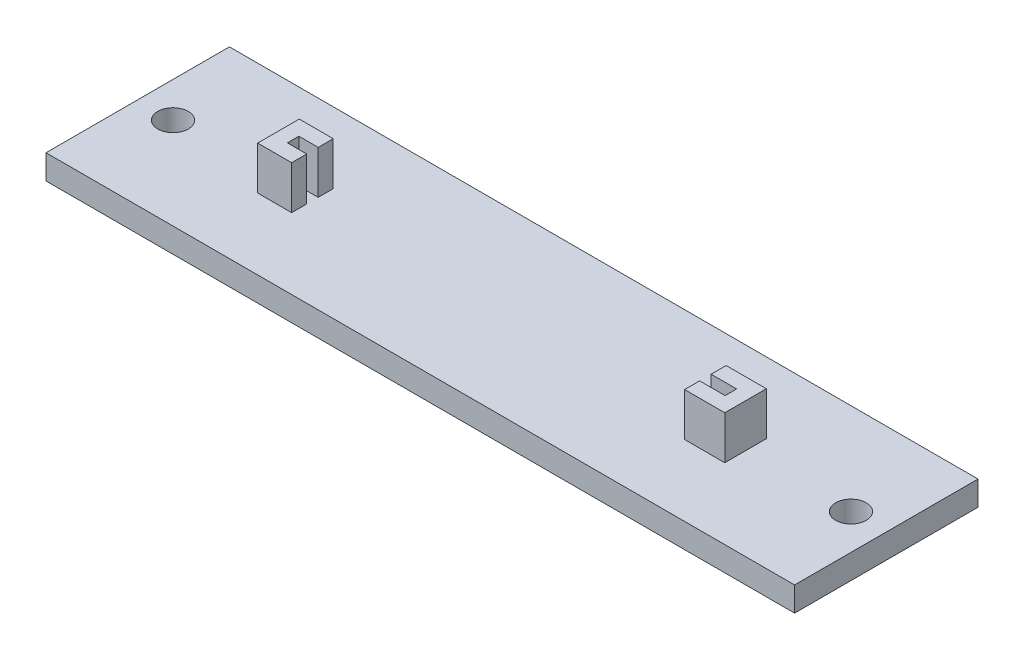
SolidWorks part; units mm, degrees
ref_plane "Front Plane" through (0, 0, 0) normal (0, 0, 1) x (1, 0, 0)
ref_plane "Top Plane" through (0, 0, 0) normal (0, 1, 0) x (1, 0, 0)
ref_plane "Right Plane" through (0, 0, 0) normal (1, 0, 0) x (0, 0, -1)
sketch "Sketch1" plane through (0, 0, 0) normal (0, 1, 0) x (1, 0, 0)
  line L1 (-38.875, 9.525) -> (38.875, 9.525)
  line L2 (-38.875, 9.525) -> (-38.875, -9.525)
  line L3 (-38.875, -9.525) -> (38.875, -9.525)
  line L4 (38.875, 9.525) -> (38.875, -9.525)
  line L5 (-38.875, 9.525) -> (38.875, -9.525) construction
  line L6 (-38.875, -9.525) -> (38.875, 9.525) construction
  point P0 (0, 0)
  dimension "D1" = 19.05
  dimension "D2" = 77.75
extrude "Boss-Extrude1" add sketch "Sketch1" along normal blind 2.54
sketch "Sketch2" plane through (0, 2.54, 0) normal (0, 1, 0) x (1, 0, 0)
  line L0 (38.875, 0) -> (36.7922, 0) construction
  line L1 (38.875, -9.525) -> (38.875, 9.525) construction
  line L2 (36.7922, 0) -> (35.2047, 0) construction
  line L3 (-38.875, 0) -> (-36.7922, 0) construction
  line L4 (-38.875, 9.525) -> (-38.875, -9.525) construction
  line L5 (-36.7922, 0) -> (-35.2047, 0) construction
  circle A0 centre (35.2047, 0) radius 1.5875
  circle A1 centre (-35.2047, 0) radius 1.5875
  dimension "D1" = 2.0828
  dimension "D2" = 1.5875
  dimension "D3" = 2.0828
  dimension "D4" = 1.5875
extrude "Cut-Extrude1" cut sketch "Sketch2" against normal through all
sketch "Sketch3" plane through (0, 2.54, 0) normal (0, 1, 0) x (1, 0, 0)
  line L1 (-24.257, 2.159) -> (24.257, 2.159)
  line L2 (-24.257, 2.159) -> (-24.257, -2.159)
  line L3 (-24.257, -2.159) -> (24.257, -2.159)
  line L4 (24.257, 2.159) -> (24.257, -2.159)
  line L5 (-24.257, 2.159) -> (24.257, -2.159) construction
  line L6 (-24.257, -2.159) -> (24.257, 2.159) construction
  point P0 (0, 0)
  dimension "D1" = 48.514
  dimension "D2" = 4.318
extrude "Boss-Extrude2" add sketch "Sketch3" along normal blind 4.4958
sketch "Sketch4" plane through (0, 7.0358, 0) normal (0, 1, 0) x (1, 0, 0)
  line L0 (-22.733, -2.159) -> (-20.7264, -2.159) construction
  line L1 (-22.733, 0.5969) -> (22.733, 0.5969)
  line L2 (-22.733, 0.5969) -> (-22.733, -0.5969)
  line L3 (-22.733, -0.5969) -> (22.733, -0.5969)
  line L4 (22.733, 0.5969) -> (22.733, -0.5969)
  line L5 (-22.733, 0.5969) -> (22.733, -0.5969) construction
  line L6 (-22.733, -0.5969) -> (22.733, 0.5969) construction
  line L7 (-24.257, -2.159) -> (24.257, -2.159) construction
  line L8 (-24.257, -2.159) -> (24.257, -2.159) construction
  line L9 (22.091, -2.159) -> (20.0844, -2.159) construction
  point P0 (0, 0)
  dimension "D1" = 45.466
  dimension "D2" = 1.1938
  dimension "D3" = 2.0066
  dimension "D4" = 2.0066
extrude "Cut-Extrude2" cut sketch "Sketch4" against normal blind 4.4958
sketch "Sketch6" plane through (0, 7.0358, 0) normal (0, 1, 0) x (1, 0, 0)
  line L0 (-20.7264, -2.159) -> (-20.7264, -0.5969)
  line L1 (-22.733, -0.5969) -> (22.733, -0.5969) construction
  line L2 (-20.7264, -2.159) -> (20.0844, -2.159)
  line L3 (20.0844, -2.159) -> (20.0844, -0.5969)
  line L4 (20.0844, -0.5969) -> (-20.7264, -0.5969)
  line L5 (-20.7264, 0.5969) -> (-20.7264, 2.159)
  line L6 (-22.733, 0.5969) -> (22.733, 0.5969) construction
  line L7 (24.257, 2.159) -> (-24.257, 2.159) construction
  line L8 (-20.7264, 2.159) -> (20.0844, 2.159)
  line L9 (20.0844, 2.159) -> (20.0844, 0.5969)
  line L10 (20.0844, 0.5969) -> (-20.7264, 0.5969)
extrude "Cut-Extrude3" cut sketch "Sketch6" against normal blind 4.4958
